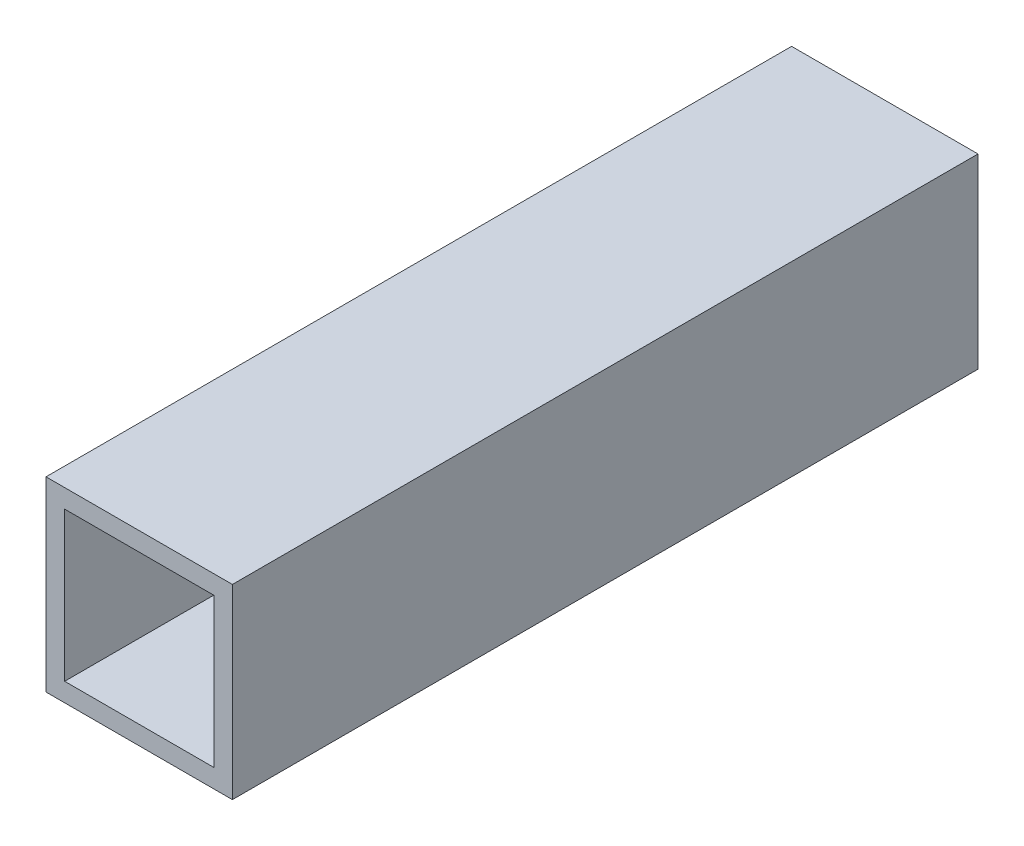
SolidWorks part; units mm, degrees
ref_plane "Front Plane" through (0, 0, 0) normal (0, 0, 1) x (1, 0, 0)
ref_plane "Top Plane" through (0, 0, 0) normal (0, 1, 0) x (1, 0, 0)
ref_plane "Right Plane" through (0, 0, 0) normal (1, 0, 0) x (0, 0, -1)
sketch "Sketch1" plane through (0, 0, 0) normal (0, 0, 1) x (1, 0, 0)
  line L0 (-20, 20) -> (-20, -20)
  line L1 (-25, 25) -> (25, 25)
  line L2 (-25, 25) -> (-25, -25)
  line L3 (-25, -25) -> (25, -25)
  line L4 (25, 25) -> (25, -25)
  line L5 (-20, -20) -> (20, -20)
  line L6 (20, 20) -> (20, -20)
  line L7 (-20, 20) -> (20, 20)
  point P9 (0, 0)
  dimension "tube_width" = 50
  dimension "D1" = 50
  dimension "D3" = 25
  dimension "D4" = 25
  dimension "tube_thickness" = 5
extrude "Boss-Extrude1" add sketch "Sketch1" along normal blind 200
sketch "Sketch3" plane through (25, 0, 0) normal (1, 0, 0) x (0, 0, -1)
  text T0 "<r90>x</r>" font "Century Gothic" height 40
  point P1 (-73.3409, -2.7599)
  point P2 (-183.1892, 0)
  point P3 (-163.465, -17.609)
  point P4 (-164.6648, -15.1639)
  point P5 (-165.0283, -12.7406)
  point P6 (0, 0)
  point P7 (0, 0)
  point P8 (-163.9556, -15.0447)
  point P9 (0, 0)
  point P10 (0, 0)
  point P11 (-164.1478, -13.7343)
  point P12 (-161.8619, -13.673)
equation "\"D1@Sketch1\"= \"tube_width@Sketch1\""
equation "\"D3@Sketch1\"=\"tube_width@Sketch1\"/2"
equation "\"D4@Sketch1\"=\"tube_width@Sketch1\"/2"
